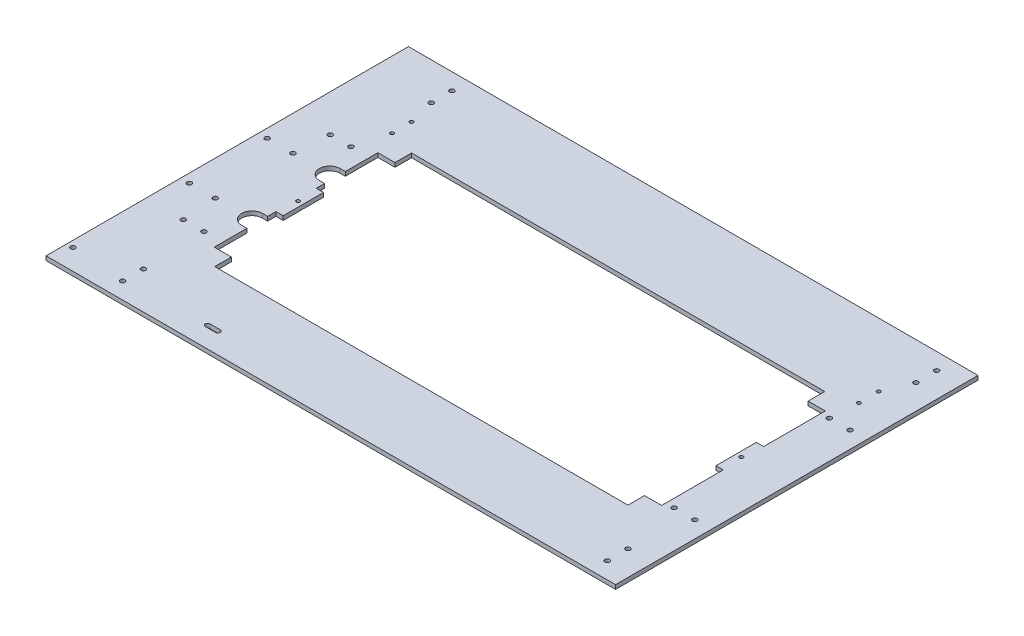
SolidWorks part; units mm, degrees
material "1060 Alloy"
ref_plane "Front Plane" through (0, 0, 0) normal (0, 0, 1) x (1, 0, 0)
ref_plane "Top Plane" through (0, 0, 0) normal (0, 1, 0) x (1, 0, 0)
ref_plane "Right Plane" through (0, 0, 0) normal (1, 0, 0) x (0, 0, -1)
sketch "Sketch1" plane through (0, 0, 0) normal (0, 1, 0) x (1, 0, 0)
  line L0 (-216, 79) -> (216, -79) construction
  line L1 (-290, -167.5) -> (260, -167.5)
  line L2 (-290, -167.5) -> (-290, 182.5)
  line L3 (-290, 182.5) -> (260, 182.5)
  line L4 (260, -167.5) -> (260, 182.5)
  line L5 (-216, -79) -> (216, -79)
  line L6 (-216, -79) -> (-216, 79)
  line L7 (-216, 79) -> (216, 79)
  line L8 (216, -79) -> (216, 79)
  dimension "D1" = 432
  dimension "D2" = 158
  dimension "D3" = 88.5
  dimension "D4" = 74
  dimension "D5" = 550
  dimension "D6" = 350
sheet metal parameters "Sheet-Metal1" thickness 4 parameters "D1"=5
base flange "Base-Flange1" sketch "Sketch1" thickness 4 reverse thickness direction no parameters "D1"=5
sketch "Sketch4" plane through (0, 0, 0) normal (0, 1, 0) x (1, 0, 0)
  line L0 (199.5, 0) -> (216, 0) construction
  line L1 (-199.5, 95) -> (199.5, 95)
  line L2 (-199.5, 95) -> (-199.5, -95)
  line L3 (-199.5, -95) -> (199.5, -95)
  line L4 (199.5, 95) -> (199.5, -95)
  line L5 (216, -79) -> (216, 79) construction
  line L6 (-199.5, 95) -> (199.5, -95) construction
  line L7 (216, 79) -> (-216, 79) construction
  line L8 (-216, 79) -> (-216, -79) construction
  dimension "D1" = 16
  dimension "D2" = 16.5
extrude "Cut-Extrude1" cut sketch "Sketch4" against normal through all normal cut yes
sketch "Sketch5" plane through (0, -4, 0) normal (0, -1, 0) x (1, 0, 0)
  line L0 (-234, 71) -> (-254, 71) construction
  line L1 (-244, 71) -> (-71.0163, 71) construction
  line L2 (-216, -79) -> (-216, 79) construction
  line L3 (224, 75) -> (244, 75) construction
  line L4 (-199.5, 95) -> (199.5, 95) construction
  line L5 (0, 95) -> (0, 116.857) construction
  line L6 (244, 75) -> (71.0163, 75) construction
  line L7 (234, 71) -> (254, 71) construction
  line L8 (-216, 79) -> (-199.5, 79) construction
  line L9 (216, 79) -> (216, -79) construction
  line L10 (0, 0) -> (-177.0468, 0) construction
  line L11 (234, -71) -> (254, -71) construction
  line L12 (244, -75) -> (71.0163, -75) construction
  line L13 (-234, -71) -> (-254, -71) construction
  line L14 (216, 0) -> (248.6013, 0) construction
  line L15 (199.5, 79) -> (216, 79) construction
  circle A0 centre (-254, 71) radius 2.25
  circle A1 centre (-234, 71) radius 2.25
  circle A2 centre (234, 71) radius 2.25 construction
  circle A3 centre (254, 71) radius 2.25 construction
  circle A4 centre (254, -71) radius 2.25 construction
  circle A5 centre (234, -71) radius 2.25 construction
  circle A6 centre (-234, -71) radius 2.25
  circle A7 centre (-254, -71) radius 2.25
  circle A8 centre (224, 75) radius 2.25
  circle A9 centre (244, 75) radius 2.25
  circle A10 centre (224, -75) radius 2.25
  circle A11 centre (244, -75) radius 2.25
  dimension "D2" = 4.5
  dimension "D4" = 18
  dimension "D5" = 8
  dimension "D1" = 20
  dimension "D3" = 8
  dimension "D6" = 4
extrude "Cut-Extrude2" cut sketch "Sketch5" against normal through all normal cut yes
sketch "Sketch6" plane through (0, 0, 0) normal (0, 1, 0) x (1, 0, 0)
  line L0 (-225.5, 121) -> (-225.5, 102) construction
  line L1 (0, 95) -> (0, 143.2453) construction
  line L2 (199.5, 95) -> (-199.5, 95) construction
  line L4 (-225.5, 111.5) -> (-199.5, 111.5) construction
  line L5 (-199.5, 111.5) -> (-199.5, 95) construction
  circle A0 centre (-225.5, 102) radius 1.75
  circle A1 centre (-225.5, 121) radius 1.75
  circle A2 centre (225.5, 102) radius 1.75
  circle A3 centre (225.5, 121) radius 1.75
  dimension "D2" = 3.5
  dimension "D1" = 19
  dimension "D3" = 16.5
  dimension "D4" = 26
extrude "Cut-Extrude3" cut sketch "Sketch6" against normal through all normal cut yes
sketch "Sketch7" plane through (0, 0, 0) normal (0, 1, 0) x (1, 0, 0)
  line L0 (199.5, 95) -> (-199.5, 95) construction
  line L1 (-199.5, 95) -> (-199.5, 79) construction
  line L2 (0, 0) -> (-290, 0) construction
  line L3 (-290, 182.5) -> (-290, -167.5) construction
  line L4 (0, 95) -> (0, 61.1102) construction
  circle A0 centre (-254.5, 115) radius 4.5
  circle A1 centre (-254.5, -115) radius 4.5
  circle A2 centre (254.5, -115) radius 4.5
  circle A3 centre (254.5, 115) radius 4.5
  dimension "D1" = 9
  dimension "D2" = 20
  dimension "D3" = 55
extrude "Cut-Extrude4" [suppressed] cut sketch "Sketch7" against normal through all normal cut yes
sketch "Sketch8" plane through (0, 0, 0) normal (0, 1, 0) x (1, 0, 0)
  line L0 (-232, 166.5) -> (-232, 146.5) construction
  line L1 (-290, 182.5) -> (-290, -167.5) construction
  line L2 (-232, -131.5) -> (-232, -151.5) construction
  line L3 (260, 182.5) -> (-290, 182.5) construction
  line L4 (-290, -167.5) -> (260, -167.5) construction
  line L5 (236, 166.5) -> (236, 146.5) construction
  line L6 (236, -131.5) -> (236, -151.5) construction
  line L7 (260, -167.5) -> (260, 182.5) construction
  circle A0 centre (-232, 146.5) radius 2.25
  circle A1 centre (-232, 166.5) radius 2.25
  circle A2 centre (-232, -151.5) radius 2.25
  circle A3 centre (-232, -131.5) radius 2.25
  circle A4 centre (236, 146.5) radius 2.25
  circle A5 centre (236, 166.5) radius 2.25
  circle A6 centre (236, -151.5) radius 2.25
  circle A7 centre (236, -131.5) radius 2.25
  dimension "D1" = 4.5
  dimension "D9" = 16
  dimension "D2" = 20
  dimension "D3" = 58
  dimension "D5" = 16
  dimension "D6" = 16
  dimension "D8" = 24
  dimension "D4" = 2
  dimension "D7" = 2
extrude "Cut-Extrude5" cut sketch "Sketch8" against normal through all normal cut yes
sketch "Sketch10" plane through (0, 0, 0) normal (0, 1, 0) x (1, 0, 0)
  line L0 (-149, -147.5) -> (-284, -147.5) construction
  line L1 (-284, -147.5) -> (-290, -147.5) construction
  line L2 (-290, 182.5) -> (-290, -167.5) construction
  line L3 (-290, -167.5) -> (260, -167.5) construction
  line L4 (-154, -147.5) -> (-144, -147.5) construction
  line L5 (-154, -145.25) -> (-144, -145.25)
  line L6 (-154, -149.75) -> (-144, -149.75)
  circle A0 centre (-284, -147.5) radius 2.25
  circle A1 centre (-149, -147.5) radius 2.25 construction
  arc A2 (-154, -145.25) -> (-154, -149.75) centre (-154, -147.5) ccw
  arc A3 (-144, -149.75) -> (-144, -145.25) centre (-144, -147.5) ccw
  point P11 (-149, -147.5)
  dimension "D2" = 4.5
  dimension "D1" = 6
  dimension "D3" = 135
  dimension "D4" = 20
  dimension "D5" = 10
extrude "Cut-Extrude7" cut sketch "Sketch10" against normal through all normal cut yes
sketch "Sketch11" plane through (0, 0, 0) normal (0, 1, 0) x (1, 0, 0)
  line L0 (-216, -79) -> (-216, 79) construction
  line L1 (-216, 19.5) -> (-209, 19.5)
  line L2 (-216, 19.5) -> (-216, -19.5)
  line L3 (-216, -19.5) -> (-209, -19.5)
  line L4 (-209, 19.5) -> (-209, -19.5)
  line L5 (-216, -19.5) -> (-216, -79) construction
  line L6 (-216, 19.5) -> (-216, 79) construction
  line L7 (-216, 79) -> (-216, 66.3542) construction
  line L8 (0, 95) -> (0, 0) construction
  line L9 (199.5, 95) -> (-199.5, 95) construction
  line L10 (216, 79) -> (216, 66.3542) construction
  line L11 (216, 19.5) -> (216, 79) construction
  line L12 (216, -19.5) -> (216, -79) construction
  line L13 (209, 19.5) -> (209, -19.5)
  line L14 (216, -19.5) -> (209, -19.5)
  line L15 (216, 19.5) -> (216, -19.5)
  line L16 (216, 19.5) -> (209, 19.5)
  dimension "D1" = 39
  dimension "D2" = 7
base flange "Tab1" sketch "Sketch11" thickness 4 reverse thickness direction no parameters "D1"=5
sketch "Sketch12" plane through (0, 0, 0) normal (0, 1, 0) x (1, 0, 0)
  line L0 (214, 0) -> (0, 0) construction
  line L1 (0, 0) -> (-214, 0) construction
  line L2 (-216, 79) -> (-216, 19.5) construction
  circle A0 centre (-214, 0) radius 1.75
  circle A1 centre (214, 0) radius 1.75
  dimension "D2" = 3.5
  dimension "D1" = 2
extrude "Cut-Extrude8" cut sketch "Sketch12" against normal through all normal cut yes
sketch "Sketch13" plane through (0, 0, 0) normal (0, 1, 0) x (1, 0, 0)
  line L0 (-221, -37.5) -> (169.7569, -37.5) construction
  line L1 (-221, -27.5) -> (169.7569, -27.5)
  line L2 (-221, -47.5) -> (169.7569, -47.5)
  line L3 (0, 0) -> (-113.688, 0) construction
  line L4 (-221, 37.5) -> (169.7569, 37.5) construction
  line L5 (-221, 27.5) -> (169.7569, 27.5)
  line L6 (-221, 47.5) -> (169.7569, 47.5)
  line L7 (-216, 79) -> (-216, 19.5) construction
  line L8 (0, 0) -> (0, 35) construction
  arc A0 (-221, -27.5) -> (-221, -47.5) centre (-221, -37.5) ccw
  arc A1 (169.7569, -47.5) -> (169.7569, -27.5) centre (169.7569, -37.5) ccw
  arc A2 (-221, 27.5) -> (-221, 47.5) centre (-221, 37.5) cw
  arc A3 (169.7569, 47.5) -> (169.7569, 27.5) centre (169.7569, 37.5) cw
  point P2 (-25.6215, -37.5)
  point P12 (-25.6215, 37.5)
  dimension "D1" = 5
  dimension "D2" = 20
  dimension "D3" = 75
extrude "Cut-Extrude9" cut sketch "Sketch13" against normal through all normal cut yes
sketch "Sketch14" plane through (0, 0, 0) normal (0, 1, 0) x (1, 0, 0)
  line L0 (-281.5, -37.5) -> (-256.5, -37.5) construction
  line L1 (-256.5, -37.5) -> (-256.5, 37.5) construction
  line L2 (-256.5, 37.5) -> (-281.5, 37.5) construction
  line L3 (-281.5, 37.5) -> (-281.5, -37.5) construction
  line L4 (-269, -37.5) -> (-269, -5.8303) construction
  line L5 (-290, 182.5) -> (-290, -167.5) construction
  line L6 (-256.5, 0) -> (-209, 0) construction
  line L7 (-209, -19.5) -> (-209, 19.5) construction
  circle A0 centre (-281.5, 37.5) radius 2.25
  circle A1 centre (-256.5, 37.5) radius 2.25
  circle A2 centre (-281.5, -37.5) radius 2.25
  circle A3 centre (-256.5, -37.5) radius 2.25
  dimension "D2" = 4.5
  dimension "D1" = 21
  dimension "D3" = 75
  dimension "D4" = 25
extrude "Cut-Extrude10" cut sketch "Sketch14" against normal through all normal cut yes
flat pattern "Flat-Pattern1" [suppressed]
sketch "Bend-Lines1" plane through (0, 0, 0) normal (0, 1, 0) x (1, 0, 0)
sketch3d "Bounding-Box1" [suppressed]
  line L0 (260, 182.5, 0) -> (-290, 182.5, 0) construction
  line L1 (260, -167.5, 0) -> (-290, -167.5, 0) construction
  line L2 (260, 182.5, 0) -> (260, -167.5, 0) construction
  line L3 (-290, 182.5, 0) -> (-290, -167.5, 0) construction
